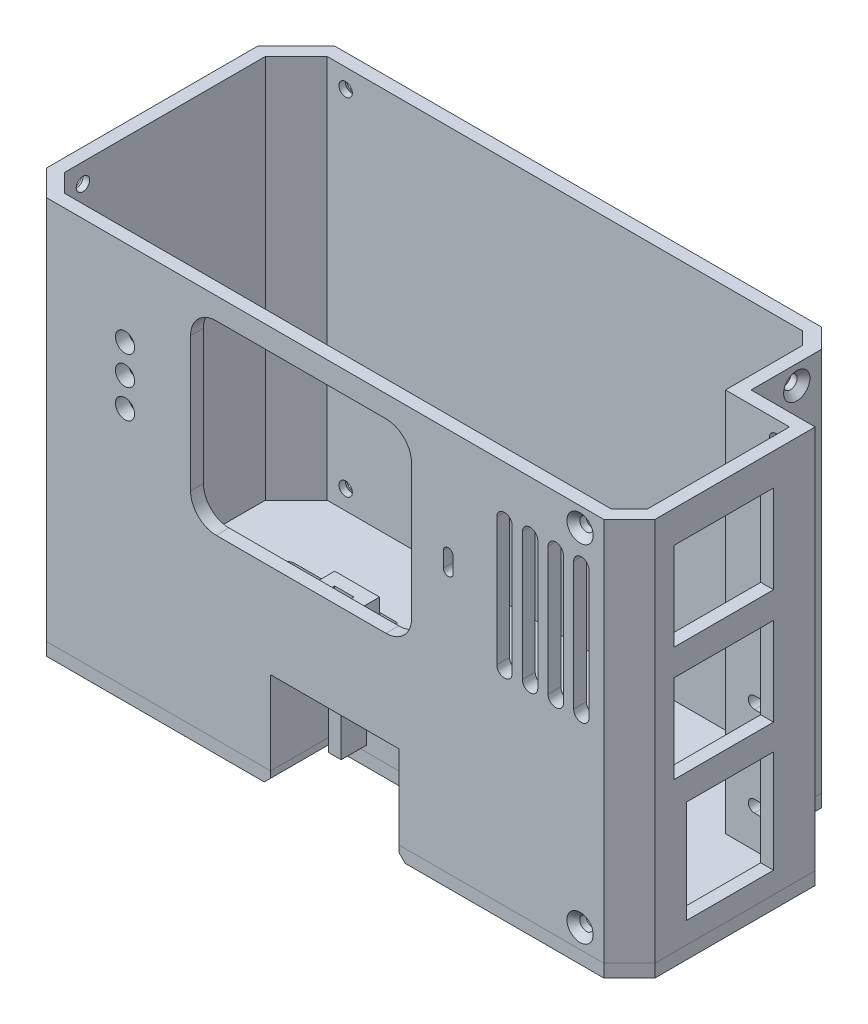
SolidWorks part; units mm, degrees
ref_plane "前视基准面" through (0, 0, 0) normal (0, 0, 1) x (1, 0, 0)
ref_plane "上视基准面" through (0, 0, 0) normal (0, 1, 0) x (1, 0, 0)
ref_plane "右视基准面" through (0, 0, 0) normal (1, 0, 0) x (0, 0, -1)
other "Configuration Table"
sketch "草图1" plane through (0, 0, 0) normal (0, 0, 1) x (1, 0, 0)
  line L1 (-105.5174, 35.9027) -> (-10.5174, 35.9027)
  line L2 (-105.5174, 35.9027) -> (-105.5174, -26.0973)
  line L3 (-105.5174, -26.0973) -> (-10.5174, -26.0973)
  line L4 (-10.5174, 35.9027) -> (-10.5174, -26.0973)
  dimension "D1" = 62
  dimension "D2" = 95
extrude "凸台-拉伸1" add sketch "草图1" along normal blind 43
sketch "草图4" plane through (0, -26.0973, 0) normal (0, -1, 0) x (1, 0, 0)
  line L0 (-10.5174, 43) -> (-10.5174, 0) construction
  line L1 (-10.5174, 14) -> (-20.5174, 14)
  line L2 (-10.5174, 14) -> (-10.5174, 0)
  line L3 (-10.5174, 0) -> (-20.5174, 0)
  line L4 (-20.5174, 14) -> (-20.5174, 0)
  line L5 (-105.5174, 0) -> (-10.5174, 0) construction
  dimension "D1" = 14
  dimension "D2" = 10
extrude "切除-拉伸3" cut sketch "草图4" against normal up to next
chamfer "倒角2" distance 6 angle 45 1 edges at (-105.5174, 4.9027, 0)
chamfer "倒角3" distance 4 angle 45 2 edges at (-105.5174, 4.9027, 43) (-10.5174, 4.9027, 43)
sketch "草图7" plane through (0, 0, 43) normal (0, 0, 1) x (1, 0, 0)
  line L0 (-101.5174, -26.0973) -> (-14.5174, -26.0973) construction
  line L1 (-46.5174, -26.0973) -> (-66.5174, -26.0973)
  line L2 (-46.5174, -26.0973) -> (-46.5174, -6.0973)
  line L3 (-46.5174, -6.0973) -> (-66.5174, -6.0973)
  line L4 (-66.5174, -26.0973) -> (-66.5174, -6.0973)
  line L6 (-10.5174, -26.0973) -> (-10.5174, 35.9027) construction
  dimension "D1" = 36
  dimension "D2" = 20
  dimension "D3" = 20
extrude "切除-拉伸5" cut sketch "草图7" against normal blind 10
shell "抽壳3" thickness 2 removed face at (-54.2952, 35.9027, 22)
sketch "草图9" plane through (0, -6.0973, 0) normal (0, -1, 0) x (1, 0, 0)
  line L0 (-44.5174, 41) -> (-68.5174, 41) construction
  line L1 (-46.5174, 41) -> (-66.5174, 41)
  line L2 (-46.5174, 41) -> (-46.5174, 33)
  line L3 (-46.5174, 33) -> (-66.5174, 33)
  line L4 (-66.5174, 41) -> (-66.5174, 33)
  line L5 (-66.5174, 33) -> (-46.5174, 33) construction
  line L8 (-66.5174, 33) -> (-66.5174, 43) construction
  line L9 (-46.5174, 33) -> (-46.5174, 43) construction
extrude "切除-拉伸6" cut sketch "草图9" against normal blind 10
sketch "草图10" plane through (0, -6.0973, 0) normal (0, -1, 0) x (1, 0, 0)
  line L4 (-66.5174, 43) -> (-66.5174, 41)
  line L5 (-66.5174, 41) -> (-46.5174, 41)
  line L6 (-46.5174, 41) -> (-46.5174, 43)
  line L7 (-46.5174, 43) -> (-66.5174, 43)
  line L8 (-66.5174, 43) -> (-66.5174, 41)
  line L9 (-66.5174, 41) -> (-46.5174, 41)
  line L10 (-46.5174, 41) -> (-46.5174, 43)
  line L11 (-46.5174, 43) -> (-66.5174, 43)
  dimension "D1" = 0
extrude "凸台-拉伸2" add sketch "草图10" along normal blind 5
sketch "草图11" plane through (0, 0, 43) normal (0, 0, 1) x (1, 0, 0)
  line L0 (-10.5174, 35.9027) -> (-10.5174, -26.0973) construction
  line L1 (-44.5174, 32.5027) -> (-79.0174, 32.5027)
  line L2 (-44.5174, 32.5027) -> (-44.5174, 3.5027)
  line L3 (-44.5174, 3.5027) -> (-79.0174, 3.5027)
  line L4 (-79.0174, 32.5027) -> (-79.0174, 3.5027)
  line L5 (-14.5174, 35.9027) -> (-101.5174, 35.9027) construction
  dimension "D1" = 34.5
  dimension "D2" = 29
  dimension "D3" = 34
  dimension "D4" = 3.4
extrude "切除-拉伸7" cut sketch "草图11" against normal blind 2
fillet "圆角5" radius 4 4 edges at (-79.0174, 32.5027, 42) (-79.0174, 3.5027, 42) (-44.5174, 32.5027, 42) (-44.5174, 3.5027, 42)
sketch "草图12" plane through (0, 0, 33) normal (0, 0, 1) x (1, 0, 0)
  line L0 (-46.5174, -4.0973) -> (-66.5174, -4.0973) construction
  line L1 (-63.5174, -4.0973) -> (-49.5174, -4.0973)
  line L2 (-63.5174, -4.0973) -> (-63.5174, -23.0973)
  line L3 (-63.5174, -23.0973) -> (-49.5174, -23.0973)
  line L4 (-49.5174, -4.0973) -> (-49.5174, -23.0973)
  line L5 (-66.5174, -4.0973) -> (-66.5174, -11.0973) construction
  line L6 (-46.5174, -4.0973) -> (-46.5174, -11.0973) construction
  line L7 (-66.5174, -26.0973) -> (-46.5174, -26.0973) construction
  dimension "D1" = 3
  dimension "D2" = 3
  dimension "D3" = 3
extrude "凸台-拉伸3" add sketch "草图12" along normal blind 4
sketch "草图13" plane through (0, -4.0973, 0) normal (0, 1, 0) x (1, 0, 0)
  line L0 (-44.5174, -31) -> (-68.5174, -31) construction
  line L1 (-61.5174, -31) -> (-51.5174, -31)
  line L2 (-61.5174, -31) -> (-61.5174, -35.5752)
  line L3 (-61.5174, -35.5752) -> (-51.5174, -35.5752)
  line L4 (-51.5174, -31) -> (-51.5174, -35.5752)
  line L5 (-68.5174, -31) -> (-68.5174, -41) construction
  line L6 (-44.5174, -31) -> (-44.5174, -41) construction
  dimension "D1" = 7
  dimension "D2" = 7
extrude "切除-拉伸8" cut sketch "草图13" against normal blind 17
sketch "草图14" plane through (0, 0, 37) normal (0, 0, 1) x (1, 0, 0)
  line L0 (-63.5174, -23.0973) -> (-49.5174, -23.0973) construction
  line L1 (-61.5174, -4.0973) -> (-51.5174, -4.0973)
  line L2 (-61.5174, -4.0973) -> (-61.5174, -23.0973)
  line L3 (-61.5174, -23.0973) -> (-51.5174, -23.0973)
  line L4 (-51.5174, -4.0973) -> (-51.5174, -23.0973)
extrude "切除-拉伸9" cut sketch "草图14" against normal up to surface (4 mm away) up to face at (-56.5174, -14.3473, 33)
chamfer "倒角4" distance 1 angle 45 2 edges at (-66.5174, -26.0973, 38) (-46.5174, -26.0973, 38)
sketch "草图15" plane through (-10.5174, 0, 0) normal (1, 0, 0) x (0, 0, -1)
  line L1 (-34.05, -4.7773) -> (-20.5, -4.7773)
  line L2 (-34.05, -4.7773) -> (-34.05, -20.7773)
  line L3 (-34.05, -20.7773) -> (-20.5, -20.7773)
  line L4 (-20.5, -4.7773) -> (-20.5, -20.7773)
  line L5 (-36, 13.0027) -> (-20.5, 13.0027)
  line L6 (-36, 13.0027) -> (-36, -0.7573)
  line L7 (-36, -0.7573) -> (-20.5, -0.7573)
  line L8 (-20.5, 13.0027) -> (-20.5, -0.7573)
  line L9 (-36, 30.9027) -> (-20.5, 30.9027)
  line L10 (-36, 30.9027) -> (-36, 17.1427)
  line L11 (-36, 17.1427) -> (-20.5, 17.1427)
  line L12 (-20.5, 30.9027) -> (-20.5, 17.1427)
extrude "切除-拉伸10" cut sketch "草图15" against normal blind 2
sketch "草图16" plane through (0, 0, 43) normal (0, 0, 1) x (1, 0, 0)
  line L0 (-38.7974, 19.2027) -> (-38.7974, 16.8027) construction
  line L1 (-38.0444, 19.2027) -> (-38.0444, 16.8027)
  line L2 (-39.5504, 19.2027) -> (-39.5504, 16.8027)
  line L3 (-44.5174, 28.5027) -> (-44.5174, 7.5027) construction
  line L5 (-44.5121, 18.0027) -> (-51.3378, 18.0027) construction
  line L6 (-10.5174, -26.0973) -> (-10.5174, 35.9027) construction
  arc A0 (-38.0444, 19.2027) -> (-39.5504, 19.2027) centre (-38.7974, 19.2027) ccw
  arc A1 (-39.5504, 16.8027) -> (-38.0444, 16.8027) centre (-38.7974, 16.8027) ccw
  point P2 (-38.7974, 18.0027)
  point P14 (-44.5174, 18.0027)
  dimension "D1" = 2.4
  dimension "D2" = 28.28
extrude "切除-拉伸11" cut sketch "草图16" against normal blind 2
sketch "草图17" plane through (0, -26.0973, 0) normal (0, -1, 0) x (1, 0, 0)
  line L0 (-105.5174, 39) -> (-105.5174, 6) construction
  line L1 (-93.9174, 13.067) -> (-84.4174, 13.067)
  line L2 (-93.9174, 13.067) -> (-93.9174, 16.567)
  line L3 (-93.9174, 16.567) -> (-84.4174, 16.567)
  line L4 (-84.4174, 13.067) -> (-84.4174, 16.567)
  line L6 (-93.9174, 20.3114) -> (-84.4174, 20.3114)
  line L7 (-93.9174, 20.3114) -> (-93.9174, 23.8114)
  line L8 (-93.9174, 23.8114) -> (-84.4174, 23.8114)
  line L9 (-84.4174, 20.3114) -> (-84.4174, 23.8114)
  line L10 (-78.1448, 23.5342) -> (-71.5448, 23.5342)
  line L11 (-78.1448, 23.5342) -> (-78.1448, 20.3114)
  line L12 (-78.1448, 20.3114) -> (-71.5448, 20.3114)
  line L13 (-71.5448, 23.5342) -> (-71.5448, 20.3114)
  line L14 (-64.6448, 23.6466) -> (-58.0448, 23.6466)
  line L15 (-64.6448, 23.6466) -> (-64.6448, 20.3114)
  line L16 (-64.6448, 20.3114) -> (-58.0448, 20.3114)
  line L17 (-58.0448, 23.6466) -> (-58.0448, 20.3114)
  line L19 (-83.4263, 17.1002) -> (-76.4263, 17.1002)
  line L20 (-83.4263, 17.1002) -> (-83.4263, 13.067)
  line L21 (-83.4263, 13.067) -> (-76.4263, 13.067)
  line L22 (-76.4263, 17.1002) -> (-76.4263, 13.067)
  line L23 (-74.9763, 17.1002) -> (-67.9763, 17.1002)
  line L24 (-74.9763, 17.1002) -> (-74.9763, 13.067)
  line L25 (-74.9763, 13.067) -> (-67.9763, 13.067)
  line L26 (-67.9763, 17.1002) -> (-67.9763, 13.067)
  line L27 (-51.5174, 16.567) -> (-43.9374, 16.567)
  line L28 (-51.5174, 16.567) -> (-51.5174, 13.767)
  line L29 (-51.5174, 13.767) -> (-43.9374, 13.767)
  line L30 (-43.9374, 16.567) -> (-43.9374, 13.767)
  line L31 (-63.5659, 16.567) -> (-52.9233, 16.567)
  line L32 (-63.5659, 16.567) -> (-63.5659, 14.767)
  line L33 (-63.5659, 14.767) -> (-52.9233, 14.767)
  line L34 (-52.9233, 16.567) -> (-52.9233, 14.767)
  dimension "D1" = 11.6
  dimension "D2" = 27.3726
  dimension "D3" = 6.9
  dimension "D4" = 6.6
  dimension "D5" = 7
  dimension "D6" = 1.45
  dimension "D7" = 9.5
  dimension "D8" = 3.5
  dimension "D9" = 2.8
  dimension "D10" = 54
  dimension "D11" = 7.58
  dimension "D12" = 1.4059
  dimension "D13" = 1.8
extrude "切除-拉伸12" cut sketch "草图17" against normal blind 2
chamfer "倒角9" distance 1 angle 45 12 edges at (-78.1448, -24.0973, 21.9228) (-74.8448, -24.0973, 23.5342) (-71.5448, -24.0973, 21.9228) (-74.8448, -24.0973, 20.3114) (-61.3448, -24.0973, 23.6466) (-64.6448, -24.0973, 21.979) (-58.0448, -24.0973, 21.979) (-61.3448, -24.0973, 20.3114) (-51.5174, -24.0973, 15.167) (-47.7274, -24.0973, 16.567) (-43.9374, -24.0973, 15.167) (-47.7274, -24.0973, 13.767)
fillet "圆角2" radius 1.2 8 edges at (-93.9174, -25.0973, 16.567) (-84.4174, -25.0973, 16.567) (-84.4174, -25.0973, 13.067) (-93.9174, -25.0973, 13.067) (-93.9174, -25.0973, 20.3114) (-93.9174, -25.0973, 23.8114) (-84.4174, -25.0973, 23.8114) (-84.4174, -25.0973, 20.3114)
fillet "圆角3" radius 0.5 18 edges at (-43.9374, -25.5973, 13.767) (-51.5174, -25.5973, 13.767) (-64.6448, -25.5973, 23.6466) (-58.0448, -25.5973, 23.6466) (-71.5448, -25.5973, 23.5342) (-78.1448, -25.5973, 23.5342) (-67.9763, -25.0973, 17.1002) (-74.9763, -25.0973, 17.1002) (-76.4263, -25.0973, 17.1002) (-83.4263, -25.0973, 17.1002) (-83.4263, -25.0973, 13.067) (-74.9763, -25.0973, 13.067) (-76.4263, -25.0973, 13.067) (-67.9763, -25.0973, 13.067) (-63.5659, -25.0973, 14.767) (-63.5659, -25.0973, 16.567) (-52.9233, -25.0973, 16.567) (-52.9233, -25.0973, 14.767)
chamfer "倒角7" distance 1 angle 45 6 edges at (-51.5174, -25.5973, 16.567) (-43.9374, -25.5973, 16.567) (-58.0448, -25.5973, 20.3114) (-64.6448, -25.5973, 20.3114) (-78.1448, -25.5973, 20.3114) (-71.5448, -25.5973, 20.3114)
sketch "草图18" plane through (0, 0, 43) normal (0, 0, 1) x (1, 0, 0)
  line L1 (-79.5174, 18.0043) -> (-81.9758, 18.0043) construction
  circle A0 centre (-89.2561, 13.5043) radius 1.5
  circle A1 centre (-89.2561, 18.0043) radius 1.5
  circle A2 centre (-89.2561, 22.5043) radius 1.5
  dimension "D3" = 3
  dimension "D2" = 3
extrude "切除-拉伸13" cut sketch "草图18" against normal blind 2
sketch "草图20" plane through (0, -24.0973, 0) normal (0, 1, 0) x (1, 0, 0)
  line L1 (-83.4263, -13.567) -> (-76.9263, -13.567)
  line L2 (-83.4263, -13.567) -> (-83.4263, -16.6002)
  line L3 (-83.4263, -16.6002) -> (-76.9263, -16.6002)
  line L4 (-76.9263, -13.567) -> (-76.9263, -16.6002)
  line L5 (-74.9763, -13.567) -> (-68.4763, -13.567)
  line L6 (-74.9763, -13.567) -> (-74.9763, -16.6002)
  line L7 (-74.9763, -16.6002) -> (-68.4763, -16.6002)
  line L8 (-68.4763, -13.567) -> (-68.4763, -16.6002)
extrude "凸台-拉伸4" add sketch "草图20" against normal blind 1
sketch "草图21" plane through (0, -25.0973, 0) normal (0, -1, 0) x (1, 0, 0)
  line L0 (-76.9263, 13.567) -> (-83.4263, 13.567) construction
  line L1 (-76.9263, 16.6002) -> (-80.9263, 16.6002)
  line L2 (-76.9263, 16.6002) -> (-76.9263, 13.567)
  line L3 (-76.9263, 13.567) -> (-80.9263, 13.567)
  line L4 (-80.9263, 16.6002) -> (-80.9263, 13.567)
  line L5 (-68.4763, 13.567) -> (-74.9763, 13.567) construction
  line L6 (-68.4763, 16.6002) -> (-72.4763, 16.6002)
  line L7 (-68.4763, 16.6002) -> (-68.4763, 13.567)
  line L8 (-68.4763, 13.567) -> (-72.4763, 13.567)
  line L9 (-72.4763, 16.6002) -> (-72.4763, 13.567)
  dimension "D1" = 4
extrude "凸台-拉伸5" add sketch "草图21" along normal up to surface (1 mm away) up to face at (-61.3448, -26.0973, 22.1299)
fillet "圆角4" radius 0.5 10 edges at (-74.9763, -25.0973, 15.0836) (-83.4263, -25.0973, 15.0836) (-80.9263, -25.5973, 13.567) (-80.9263, -25.5973, 16.6002) (-72.4763, -25.5973, 16.6002) (-72.4763, -25.5973, 13.567) (-68.4763, -25.0973, 16.6002) (-68.4763, -25.0973, 13.567) (-76.9263, -25.0973, 13.567) (-76.9263, -25.0973, 16.6002)
chamfer "倒角10" distance 2 angle 45 1 edges at (-22.5174, 5.9027, 2)
chamfer "倒角11" distance 3 angle 45 1 edges at (-20.5174, 4.9027, 0)
sketch "草图26" plane through (-20.5174, 0, 0) normal (1, 0, 0) x (0, 0, -1)
  line L0 (-10, 18.9027) -> (-10, -21.0973) construction
  line L1 (-8.6566, 18.9027) -> (-8.6566, -21.0973)
  line L2 (-11.3434, 18.9027) -> (-11.3434, -21.0973)
  line L3 (-14, -26.0973) -> (-3, -26.0973) construction
  line L5 (0, 35.9027) -> (0, -26.0973) construction
  arc A0 (-8.6566, 18.9027) -> (-11.3434, 18.9027) centre (-10, 18.9027) ccw
  arc A1 (-11.3434, -21.0973) -> (-8.6566, -21.0973) centre (-10, -21.0973) ccw
  point P2 (-10, -1.0973)
  dimension "D1" = 40
  dimension "D2" = 25
  dimension "D3" = 10
extrude "切除-拉伸15" cut sketch "草图26" against normal up to next
sketch "草图27" plane through (0, 0, 43) normal (0, 0, 1) x (1, 0, 0)
  line L1 (-18.0174, 27.9027) -> (-18.0174, 7.9027) construction
  line L8 (-16.8174, 27.9027) -> (-16.8174, 7.9027)
  line L17 (-19.2174, 27.9027) -> (-19.2174, 7.9027)
  line L25 (-14.5174, 35.9027) -> (-101.5174, 35.9027) construction
  line L28 (-10.5174, 35.9027) -> (-10.5174, -26.0973) construction
  line L31 (-22.0174, 27.9027) -> (-22.0174, 7.9027) construction
  line L34 (-20.8174, 27.9027) -> (-20.8174, 7.9027)
  line L37 (-23.2174, 27.9027) -> (-23.2174, 7.9027)
  line L38 (-26.0174, 27.9027) -> (-26.0174, 7.9027) construction
  line L39 (-24.8174, 27.9027) -> (-24.8174, 7.9027)
  line L40 (-27.2174, 27.9027) -> (-27.2174, 7.9027)
  line L41 (-30.0174, 27.9027) -> (-30.0174, 7.9027) construction
  line L42 (-28.8174, 27.9027) -> (-28.8174, 7.9027)
  line L43 (-31.2174, 27.9027) -> (-31.2174, 7.9027)
  arc A44 (-16.8174, 27.9027) -> (-19.2174, 27.9027) centre (-18.0174, 27.9027) ccw
  arc A45 (-19.2174, 7.9027) -> (-16.8174, 7.9027) centre (-18.0174, 7.9027) ccw
  arc A46 (-20.8174, 27.9027) -> (-23.2174, 27.9027) centre (-22.0174, 27.9027) ccw
  arc A47 (-23.2174, 7.9027) -> (-20.8174, 7.9027) centre (-22.0174, 7.9027) ccw
  arc A48 (-24.8174, 27.9027) -> (-27.2174, 27.9027) centre (-26.0174, 27.9027) ccw
  arc A49 (-27.2174, 7.9027) -> (-24.8174, 7.9027) centre (-26.0174, 7.9027) ccw
  arc A50 (-28.8174, 27.9027) -> (-31.2174, 27.9027) centre (-30.0174, 27.9027) ccw
  arc A51 (-31.2174, 7.9027) -> (-28.8174, 7.9027) centre (-30.0174, 7.9027) ccw
  point P2 (-18.0174, 17.9027)
  point P14 (-22.0174, 17.9027)
  point P21 (-26.0174, 17.9027)
  point P28 (-30.0174, 17.9027)
  dimension "D3" = 20
  dimension "D4" = 1.2
  dimension "D1" = 8
  dimension "D2" = 7.5
  dimension "D5" = 4
sketch "草图29" plane through (-105.5174, 0, 0) normal (-1, 0, 0) x (0, 0, 1)
  line L0 (39, -26.0973) -> (6, -26.0973) construction
  circle A0 centre (35.3017, 32.9027) radius 1.05
  circle A1 centre (35.3017, -21.0973) radius 1.2021
  dimension "D1" = 2.1
  dimension "D2" = 5
extrude "切除-拉伸18" cut sketch "草图29" against normal up to next
sketch "草图30" plane through (0, 0, 0) normal (0, 0, -1) x (-1, 0, 0)
  line L0 (99.5174, -26.0973) -> (23.5174, -26.0973) construction
  circle A0 centre (95.8191, 32.9027) radius 1.05
  circle A1 centre (95.8191, -21.0973) radius 1.05
  dimension "D1" = 2.1
  dimension "D2" = 5
extrude "切除-拉伸19" cut sketch "草图30" against normal up to next
sketch "草图31" plane through (-20.5174, 0, 0) normal (1, 0, 0) x (0, 0, -1)
  line L0 (-14, -26.0973) -> (-3, -26.0973) construction
  circle A0 centre (-6.8698, 32.9027) radius 1.05
  circle A1 centre (-6.8698, -21.0973) radius 1.05
  dimension "D1" = 2.1
  dimension "D2" = 5
extrude "切除-拉伸20" cut sketch "草图31" against normal up to next
sketch "草图32" plane through (0, 0, 14) normal (0, 0, -1) x (-1, 0, 0)
  line L0 (10.5174, -26.0973) -> (20.5174, -26.0973) construction
  circle A0 centre (14.6174, 32.9027) radius 1.05
  circle A1 centre (14.6174, -21.0973) radius 1.05
  dimension "D1" = 2.1
  dimension "D2" = 5
extrude "切除-拉伸21" cut sketch "草图32" against normal up to next
sketch "草图33" plane through (0, 0, 43) normal (0, 0, 1) x (1, 0, 0)
  line L1 (-45.5174, -26.0973) -> (-14.5174, -26.0973) construction
  circle A0 centre (-18.2157, 32.9027) radius 1.05
  circle A1 centre (-18.2157, -21.0973) radius 1.05
  dimension "D1" = 2.1
  dimension "D2" = 5
extrude "切除-拉伸22" cut sketch "草图33" against normal up to next
chamfer "倒角20" distance 1 angle 45 10 edges at (-96.8691, 32.9027, 0) (-105.5174, 31.8527, 35.3017) (-17.1657, 32.9027, 43) (-15.6674, 32.9027, 14) (-20.5174, 32.9027, 5.8198) (-17.1657, -21.0973, 43) (-15.6674, -21.0973, 14) (-96.8691, -21.0973, 0) (-105.5174, -22.2995, 35.3017) (-20.5174, -21.0973, 5.8198)
sketch "草图34" plane through (0, 0, 14) normal (0, 0, -1) x (-1, 0, 0)
  line L0 (18.0174, -4.0973) -> (14.0174, -4.0973) construction
  line L1 (18.0174, -5.0973) -> (14.0174, -5.0973)
  line L2 (18.0174, -3.0973) -> (14.0174, -3.0973)
  line L3 (18.0174, -18.0973) -> (14.0174, -18.0973) construction
  line L4 (18.0174, -19.0973) -> (14.0174, -19.0973)
  line L5 (18.0174, -17.0973) -> (14.0174, -17.0973)
  line L7 (20.5174, 35.9027) -> (20.5174, -26.0973) construction
  arc A0 (18.0174, -5.0973) -> (18.0174, -3.0973) centre (18.0174, -4.0973) ccw
  arc A1 (14.0174, -3.0973) -> (14.0174, -5.0973) centre (14.0174, -4.0973) ccw
  arc A2 (18.0174, -19.0973) -> (18.0174, -17.0973) centre (18.0174, -18.0973) ccw
  arc A3 (14.0174, -17.0973) -> (14.0174, -19.0973) centre (14.0174, -18.0973) ccw
  point P3 (16.0174, -4.0973)
  point P8 (16.0174, -18.0973)
  dimension "D1" = 1
  dimension "D2" = 4
  dimension "D3" = 2.5
  dimension "D4" = 14
extrude "切除-拉伸25" cut sketch "草图34" against normal up to next (2 mm away) draft 2
extrude "切除-拉伸26" cut sketch "草图27" against normal up to next
split "分割1" bodies to split 138 resulting bodies 139 140 split by face at (-47.7274, -24.0973, 15.167)
